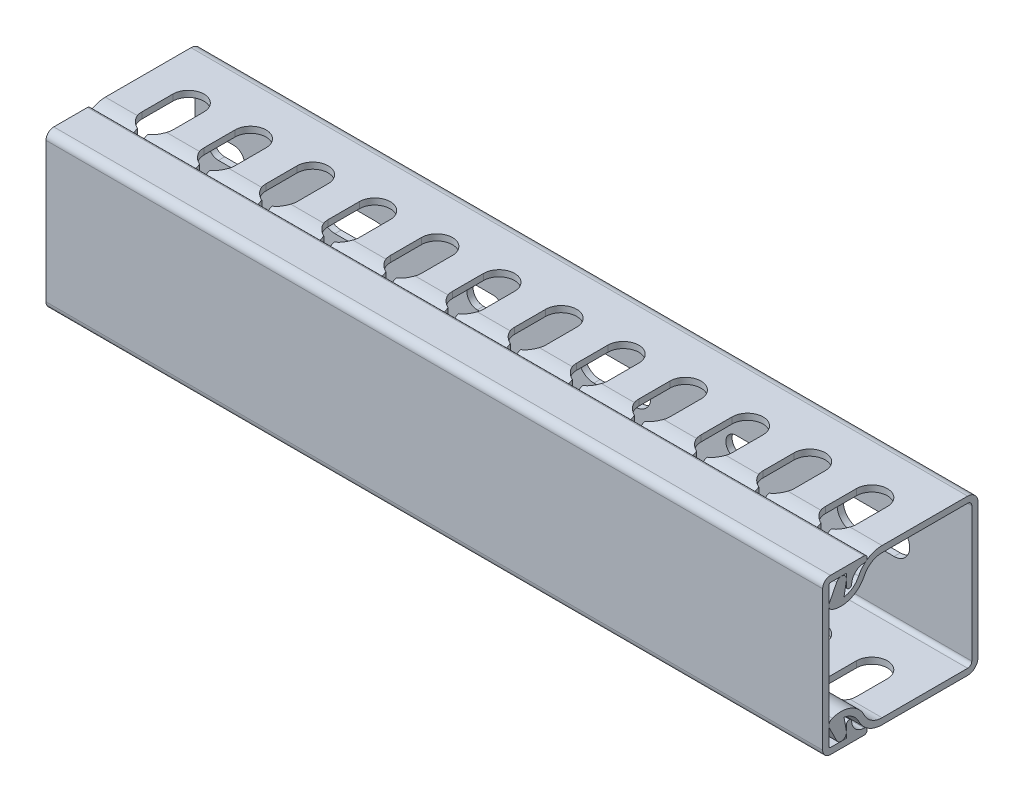
SolidWorks part; units mm, degrees
ref_plane "Front" through (0, 0, 0) normal (0, 0, 1) x (1, 0, 0)
ref_plane "Top" through (0, 0, 0) normal (0, 1, 0) x (1, 0, 0)
ref_plane "Right" through (0, 0, 0) normal (1, 0, 0) x (0, 0, -1)
sketch "Sketch1" plane through (0, 0, 0) normal (1, 0, 0) x (0, 0, -1)
  line L0 (-25.4152, -12.6264) -> (-25.8698, -10.0482)
  line L1 (0, -15) -> (-18.5359, -15)
  line L5 (-27.2927, -13.2506) -> (-28.6927, -10.4771)
  line L6 (-26.4732, -11) -> (-23.2292, -11) construction
  line L7 (0, 0) -> (-35.6549, 0) construction
  line L8 (0, 0) -> (0, -15)
  line L9 (-30, 0) -> (-30, -15)
  line L10 (-30, -15) -> (-22, -15)
  line L11 (-25.4, -11.5) -> (-25.4, -13.8)
  line L12 (-25.4, -13.8) -> (-28.8, -13.8)
  line L13 (-28.8, -13.8) -> (-28.8, 13.8)
  line L15 (-21.4, -11) -> (-21.4, -18.4358) construction
  line L16 (-1.2, 0) -> (-1.2, -13.8)
  line L17 (-1.2, -13.8) -> (-18.5359, -13.8)
  line L19 (-21.9633, -11.6409) -> (-23.6964, -8.021) construction
  line L20 (-28.8, -8.8) -> (-24.4003, -8.8) construction
  line L21 (-28.8, 8.8) -> (-24.4003, 8.8) construction
  line L22 (-21.4, 11) -> (-21.4, 18.4358) construction
  line L23 (-23.0457, -12.1591) -> (-24.7788, -8.5392) construction
  line L24 (-26.4732, 11) -> (-23.2292, 11) construction
  line L25 (-1.2, 13.8) -> (-18.5359, 13.8)
  line L26 (-1.2, 0) -> (-1.2, 13.8)
  line L27 (-25.4, 13.8) -> (-28.8, 13.8)
  line L28 (-25.4, 11.5) -> (-25.4, 13.8)
  line L29 (-30, 15) -> (-22, 15)
  line L30 (-30, 0) -> (-30, 15)
  line L31 (0, 0) -> (0, 15)
  line L32 (-27.2927, 13.2506) -> (-28.6927, 10.4771)
  line L33 (0, 15) -> (-18.5359, 15)
  line L34 (-25.4152, 12.6264) -> (-25.8698, 10.0482)
  arc A0 (-25.8698, -10.0482) -> (-23.0457, -12.1591) centre (-26.4732, -13.8) cw
  arc A1 (-22, -15) -> (-22, -13.8) centre (-22, -14.4) ccw
  arc A2 (-22, -13.8) -> (-24.4003, -11.4825) centre (-22, -11.3982) cw
  arc A3 (-24.4003, -11.4825) -> (-25.4, -11.5) centre (-24.9, -11.5) ccw
  arc A4 (-23.0457, -12.1591) -> (-18.5359, -15) centre (-18.5359, -10) ccw
  arc A5 (-25.4152, -12.6264) -> (-27.2927, -13.2506) centre (-26.4, -12.8) cw
  arc A6 (-21.9633, -11.6409) -> (-18.5359, -13.8) centre (-18.5359, -10) ccw
  arc A7 (-28.1317, -9.0831) -> (-21.9633, -11.6409) centre (-26.4732, -13.8) cw
  arc A8 (-25.6793, -8.8634) -> (-21.9633, -11.6409) centre (-26.4732, -13.8) cw construction
  arc A9 (-28.1317, -9.0831) -> (-28.6927, -10.4771) centre (-27.8, -10.0265) ccw
  arc A10 (-28.1317, 9.0831) -> (-28.6927, 10.4771) centre (-27.8, 10.0265) cw
  arc A11 (-28.1317, 9.0831) -> (-21.9633, 11.6409) centre (-26.4732, 13.8) ccw
  arc A12 (-21.9633, 11.6409) -> (-18.5359, 13.8) centre (-18.5359, 10) cw
  arc A13 (-25.4152, 12.6264) -> (-27.2927, 13.2506) centre (-26.4, 12.8) ccw
  arc A14 (-23.0457, 12.1591) -> (-18.5359, 15) centre (-18.5359, 10) cw
  arc A15 (-24.4003, 11.4825) -> (-25.4, 11.5) centre (-24.9, 11.5) cw
  arc A16 (-22, 13.8) -> (-24.4003, 11.4825) centre (-22, 11.3982) ccw
  arc A17 (-22, 15) -> (-22, 13.8) centre (-22, 14.4) cw
  arc A18 (-25.8698, 10.0482) -> (-23.0457, 12.1591) centre (-26.4732, 13.8) ccw
  point P31 (-20, -15)
  point P61 (-28.8, 0)
  point P62 (-20, 15)
  dimension "D2" = 20
  dimension "D6" = 1.2
  dimension "D8" = 0.6
  dimension "D11" = 0.5
  dimension "D4" = 1
  dimension "D5" = 5
  dimension "D13" = 5
  dimension "D15" = 5
  dimension "D16" = 1
  dimension "D1" = 30
  dimension "D7" = 1.2
  dimension "D9" = 3.4
  dimension "D10" = 1.2
  dimension "D12" = 4
  dimension "D17" = 10
  dimension "D18" = 4
  dimension "D3" = 30
  dimension "D14" = 1.2
extrude "Boss-Extrude1" add sketch "Sketch1" along normal blind 150 contours A18 L34 A13 L32 A10 A11 A12 L25 L26 L16 L17 A6 A7 A9 L5 A5 L0 A0 A4 L1 L8 L31 L33 A14 | A17 L29 L30 L9 L10 A1 A2 A3 L11 L12 L13 L27 L28 A15 A16 region at (0, -12.7491, 25.8181) region at (0, -12.15, 25.0879)
sketch "Sketch2" plane through (0, 0, 0) normal (0, 1, 0) x (1, 0, 0)
  line L0 (9, -11.5) -> (9, -17.5) construction
  line L1 (12, -11.5) -> (12, -17.5)
  line L2 (6, -11.5) -> (6, -17.5)
  line L3 (150, 0) -> (0, 0) construction
  line L5 (8, -20.3284) -> (8, -30.388)
  line L6 (8, -30.388) -> (10, -30.388)
  line L7 (10, -20.3284) -> (10, -30.388)
  line L8 (8, -20.3284) -> (10, -30.388) construction
  line L9 (8, -30.388) -> (10, -20.3284) construction
  line L10 (0, 0) -> (0, -18.5359) construction
  arc A0 (12, -11.5) -> (6, -11.5) centre (9, -11.5) ccw
  arc A1 (6, -17.5) -> (8, -20.3284) centre (9, -17.5) ccw
  arc A2 (10, -20.3284) -> (12, -17.5) centre (9, -17.5) ccw
  point P2 (10.517, -14.5)
  point P7 (9, -25.3582)
  dimension "D1" = 6
  dimension "D2" = 6
  dimension "D3" = 11.5
  dimension "D4" = 2
  dimension "D5" = 6
extrude "Cut-Extrude1" cut sketch "Sketch2" against normal through all both and the other way through all
sketch "Sketch4" plane through (0, 0, 0) normal (0, 0, 1) x (1, 0, 0)
  line L0 (0, 0) -> (150, 0) construction
  line L1 (150, -13.8) -> (150, 13.8) construction
  line L2 (4.5, 0) -> (7.5, 0) construction
  line L3 (4.5, 2) -> (7.5, 2)
  line L4 (4.5, -2) -> (7.5, -2)
  line L5 (27, 0) -> (35, 0) construction
  line L6 (27, 3) -> (35, 3)
  line L7 (27, -3) -> (35, -3)
  line L8 (0, -13.8) -> (0, 13.8) construction
  arc A0 (4.5, 2) -> (4.5, -2) centre (4.5, 0) ccw
  arc A1 (7.5, -2) -> (7.5, 2) centre (7.5, 0) ccw
  arc A2 (27, 3) -> (27, -3) centre (27, 0) ccw
  arc A3 (35, -3) -> (35, 3) centre (35, 0) ccw
  point P7 (6, 0)
  point P12 (31, 0)
  dimension "D1" = 6
  dimension "D2" = 8
  dimension "D3" = 3
  dimension "D4" = 4
  dimension "D5" = 25
  dimension "D6" = 6
extrude "Cut-Extrude3" cut sketch "Sketch4" along normal through all
pattern_linear "LPattern1" count 12 spacing 12 along (1, 0, 0) of "Cut-Extrude1"
pattern_linear "LPattern2" count 3 spacing 50 along (1, 0, 0) of "Cut-Extrude3"
fillet "Fillet1" radius 1.5 2 edges at (75, -15, 30) (75, 15, 30)
fillet "Fillet2" radius 2 2 edges at (75, -15, 0) (75, 15, 0)
fillet "Fillet3" radius 0.8 2 edges at (75, -13.8, 1.2) (75, 13.8, 1.2)
fillet "Fillet4" radius 0.3 2 edges at (75, -13.8, 28.8) (75, 13.8, 28.8)
equation "\"Length\"=150"
equation "\"Slot spacing\"= 12"
equation "\"D1@Boss-Extrude1\"=\"Length\""
equation "\"D3@LPattern1\"=\"Slot spacing\""
